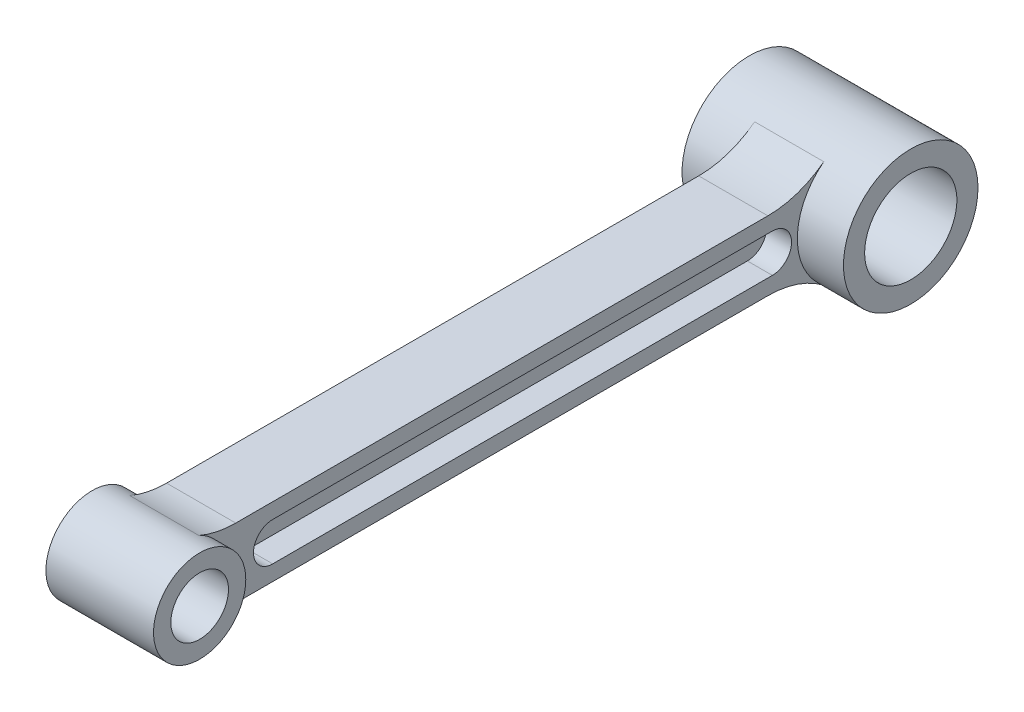
SolidWorks part; units mm, degrees
ref_plane "Front Plane" through (0, 0, 0) normal (0, 0, 1) x (1, 0, 0)
ref_plane "Top Plane" through (0, 0, 0) normal (0, 1, 0) x (1, 0, 0)
ref_plane "Right Plane" through (0, 0, 0) normal (1, 0, 0) x (0, 0, -1)
sketch "Sketch1" plane through (0, 0, 0) normal (1, 0, 0) x (0, 0, -1)
  line L0 (0, 0) -> (130, 0) construction
  line L1 (0, 5) -> (130, 5)
  line L2 (0, -5) -> (130, -5)
  line L4 (-9.6125, -9) -> (129.6982, -9)
  line L5 (-9.6125, 9) -> (128.8355, 9)
  arc A0 (0, 5) -> (0, -5) centre (0, 0) ccw
  arc A1 (130, -5) -> (130, 5) centre (130, 0) ccw
  circle A2 centre (154, 0) radius 12
  circle A3 centre (-24, 0) radius 12
  circle A4 centre (-24, 0) radius 7.5
  circle A5 centre (154, 0) radius 17.5
  arc A6 (128.8355, 9) -> (143.3885, 13.9157) centre (128.8355, 33) ccw
  arc A7 (-19.2042, 11) -> (-9.6125, 9) centre (-9.6125, 33) ccw
  arc A8 (128.8355, -9) -> (143.3885, -13.9157) centre (128.8355, -33) cw
  arc A9 (-19.2042, -11) -> (-9.6125, -9) centre (-9.6125, -33) cw
  point P3 (65, 0)
  point P16 (-24, 9)
  point P17 (154, 9)
  dimension "D2" = 5
  dimension "D3" = 15
  dimension "D4" = 24
  dimension "D5" = 24
  dimension "D6" = 35
  dimension "D11" = 48
  dimension "D12" = 48
  dimension "D1" = 130
  dimension "D7" = 178
  dimension "D8" = 24
extrude "Boss-Extrude1" add sketch "Sketch1" along normal mid plane 5 contours L2 A1 L1 A0 region at (0, 0, -65)
extrude "Boss-Extrude2" add sketch "Sketch1<3>" along normal mid plane 42 separate body contours A5 A2 region at (0, 0, -136.995)
sketch "Sketch1<3>" plane through (0, 0, 0) normal (1, 0, 0) x (0, 0, -1) same geometry as "Sketch1"
extrude "Boss-Extrude3" add sketch "Sketch1<4>" along normal mid plane 28 separate body contours A3 A4 region at (0, 0, 35.6606)
sketch "Sketch1<4>" plane through (0, 0, 0) normal (1, 0, 0) x (0, 0, -1) same geometry as "Sketch1"
extrude "Boss-Extrude4" add sketch "Sketch1<5>" along normal mid plane 18 contours A3 A9 L4 A8 A5 A6 L5 A7 A1 L2 A0 L1 region at (0, -7.8905, 14.8482)
sketch "Sketch1<5>" plane through (0, 0, 0) normal (1, 0, 0) x (0, 0, -1) same geometry as "Sketch1"
